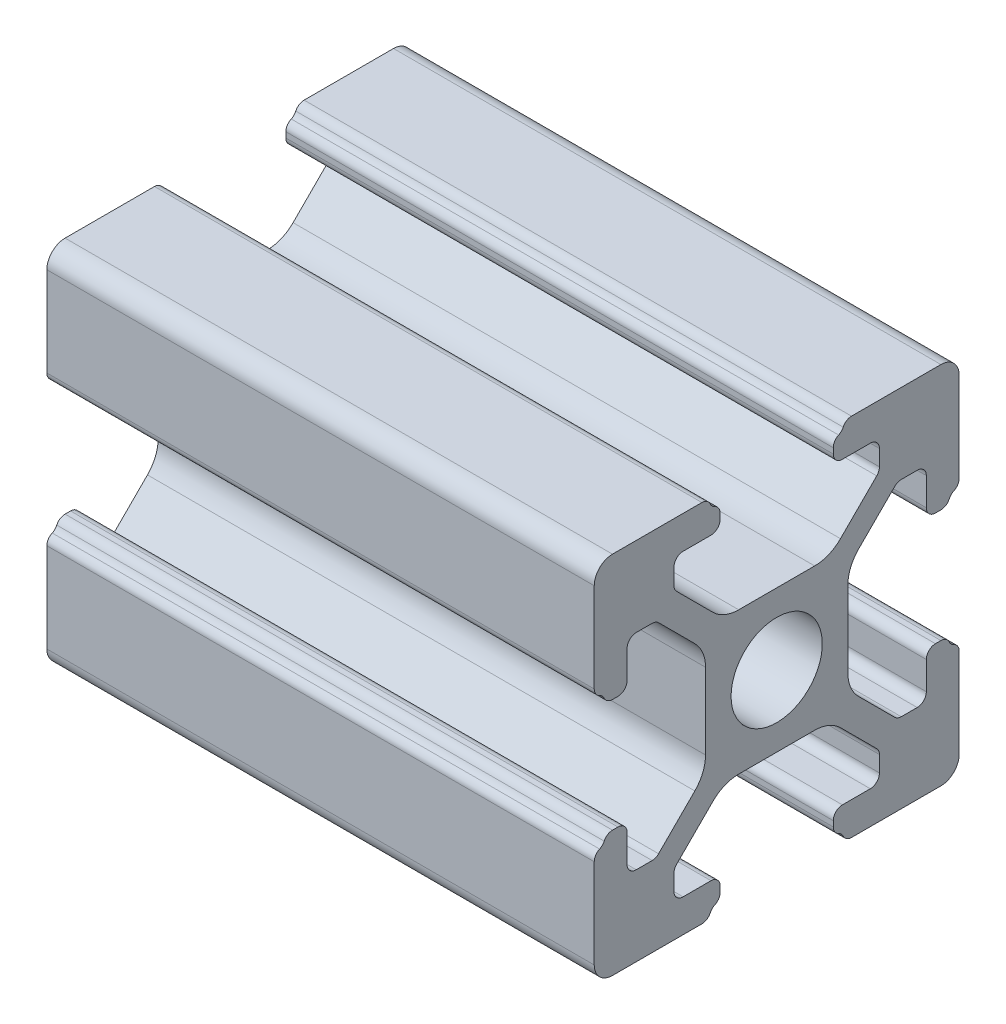
SolidWorks part; units mm, degrees
ref_plane "Front Plane" through (0, 0, 0) normal (0, 0, 1) x (1, 0, 0)
ref_plane "Top Plane" through (0, 0, 0) normal (0, 1, 0) x (1, 0, 0)
ref_plane "Right Plane" through (0, 0, 0) normal (1, 0, 0) x (0, 0, -1)
sketch "Sketch1" plane through (0, 0, 0) normal (1, 0, 0) x (0, 0, -1)
  line L0 (10, 10) -> (-10, -10) construction
  line L1 (-10, 10) -> (10, 10)
  line L2 (-10, 10) -> (-10, -10)
  line L3 (-10, -10) -> (10, -10)
  line L4 (10, 10) -> (10, -10)
  dimension "D1" = 20
extrude "Boss-Extrude1" add sketch "Sketch1" along normal blind 30
fillet "Fillet1" radius 1 4 edges at (15, -10, -10) (15, -10, 10) (15, 10, -10) (15, 10, 10)
sketch "Sketch3" plane through (0, 0, 0) normal (-1, 0, 0) x (0, 0, 1)
  line L0 (-3.6, 10) -> (3.6, 10)
  line L1 (-9, 10) -> (9, 10) construction
  line L2 (3.6, 10) -> (3.6, 9.5)
  line L3 (3.6, 9.5) -> (3.1, 9.5)
  line L4 (3.1, 9.5) -> (3.1, 8.2)
  line L5 (3.1, 8.2) -> (5.63, 8.2)
  line L6 (5.63, 8.2) -> (5.63, 6.6199)
  line L7 (5.63, 6.6199) -> (2.9101, 3.9)
  line L8 (2.9101, 3.9) -> (-2.9101, 3.9)
  line L9 (-2.9101, 3.9) -> (-5.63, 6.6199)
  line L10 (-5.63, 6.6199) -> (-5.63, 8.2)
  line L11 (-5.63, 8.2) -> (-3.1, 8.2)
  line L12 (-3.1, 8.2) -> (-3.1, 9.5)
  line L13 (-3.1, 9.5) -> (-3.6, 9.5)
  line L14 (-3.6, 9.5) -> (-3.6, 10)
  line L15 (0, 10) -> (0, 3.9) construction
  line L16 (10, 3.6) -> (10, -3.6)
  line L17 (10, -3.6) -> (9.5, -3.6)
  line L18 (9.5, -3.6) -> (9.5, -3.1)
  line L19 (9.5, -3.1) -> (8.2, -3.1)
  line L20 (8.2, -3.1) -> (8.2, -5.63)
  line L21 (8.2, -5.63) -> (6.6199, -5.63)
  line L22 (6.6199, -5.63) -> (3.9, -2.9101)
  line L23 (3.9, -2.9101) -> (3.9, 2.9101)
  line L24 (3.9, 2.9101) -> (6.6199, 5.63)
  line L25 (6.6199, 5.63) -> (8.2, 5.63)
  line L26 (8.2, 5.63) -> (8.2, 3.1)
  line L27 (8.2, 3.1) -> (9.5, 3.1)
  line L28 (9.5, 3.1) -> (9.5, 3.6)
  line L29 (9.5, 3.6) -> (10, 3.6)
  line L30 (10, 0) -> (3.9, 0) construction
  line L31 (3.6, -10) -> (-3.6, -10)
  line L32 (-3.6, -10) -> (-3.6, -9.5)
  line L33 (-3.6, -9.5) -> (-3.1, -9.5)
  line L34 (-3.1, -9.5) -> (-3.1, -8.2)
  line L35 (-3.1, -8.2) -> (-5.63, -8.2)
  line L36 (-5.63, -8.2) -> (-5.63, -6.6199)
  line L37 (-5.63, -6.6199) -> (-2.9101, -3.9)
  line L38 (-2.9101, -3.9) -> (2.9101, -3.9)
  line L39 (2.9101, -3.9) -> (5.63, -6.6199)
  line L40 (5.63, -6.6199) -> (5.63, -8.2)
  line L41 (5.63, -8.2) -> (3.1, -8.2)
  line L42 (3.1, -8.2) -> (3.1, -9.5)
  line L43 (3.1, -9.5) -> (3.6, -9.5)
  line L44 (3.6, -9.5) -> (3.6, -10)
  line L45 (0, -10) -> (0, -3.9) construction
  line L46 (-10, -3.6) -> (-10, 3.6)
  line L47 (-10, 3.6) -> (-9.5, 3.6)
  line L48 (-9.5, 3.6) -> (-9.5, 3.1)
  line L49 (-9.5, 3.1) -> (-8.2, 3.1)
  line L50 (-8.2, 3.1) -> (-8.2, 5.63)
  line L51 (-8.2, 5.63) -> (-6.6199, 5.63)
  line L52 (-6.6199, 5.63) -> (-3.9, 2.9101)
  line L53 (-3.9, 2.9101) -> (-3.9, -2.9101)
  line L54 (-3.9, -2.9101) -> (-6.6199, -5.63)
  line L55 (-6.6199, -5.63) -> (-8.2, -5.63)
  line L56 (-8.2, -5.63) -> (-8.2, -3.1)
  line L57 (-8.2, -3.1) -> (-9.5, -3.1)
  line L58 (-9.5, -3.1) -> (-9.5, -3.6)
  line L59 (-9.5, -3.6) -> (-10, -3.6)
  line L60 (-10, 0) -> (-3.9, 0) construction
  line L61 (10, 9) -> (10, -9) construction
  line L62 (-10, -9) -> (-10, 9) construction
  point P4 (0, 10)
  point P17 (0, 0)
  point P26 (10, 0)
  point P43 (0, -10)
  point P60 (-10, 0)
  point P75 (0, 0)
  dimension "D1" = 135
  dimension "D2" = 6.2
  dimension "D3" = 7.2
  dimension "D4" = 6.1
  dimension "D5" = 11.26
  dimension "D6" = 0.5
  dimension "D8" = 1.4
  dimension "D9" = 1.8
  dimension "D7" = 4
extrude "Cut-Extrude1" cut sketch "Sketch3" against normal through all
hole_wizard "Ø5.0 (5) Diameter Hole1" positions "Sketch4" profile "Sketch5" hole size "Ø5.0" standard "ANSI Metric" end condition through all
sketch "Sketch4" plane through (0, 0, 0) normal (-1, 0, 0) x (0, 0, 1)
  point P0 (0, 0)
sketch "Sketch5" plane through (0, 0, 0) normal (0, 1, 0) x (0, 0, 1)
  line L0 (0, 0) -> (0, 30)
  line L1 (0, 30) -> (2.5, 30)
  line L2 (2.5, 30) -> (2.5, 0)
  line L5 (2.5, 0) -> (0, 0)
  line L11 (0, -6.35) -> (0, 107.95) construction
  dimension "Thru Hole Dia." = 5
  dimension "Thru Hole Depth" = 30
fillet "Fillet2" radius 2 8 edges at (15, -3.9, -2.9101) (15, -3.9, 2.9101) (15, -2.9101, 3.9) (15, 2.9101, 3.9) (15, 3.9, 2.9101) (15, 3.9, -2.9101) (15, 2.9101, -3.9) (15, -2.9101, -3.9)
fillet "Fillet3" radius 0.5 20 edges at (15, 3.6, -10) (15, 3.1, -9.5) (15, 3.1, -8.2) (15, 5.63, -8.2) (15, 5.63, -6.6199) (15, 3.6, 10) (15, 3.1, 9.5) (15, 3.1, 8.2) (15, 5.63, 8.2) (15, 5.63, 6.6199) (15, 6.6199, 5.63) (15, 8.2, 5.63) (15, 8.2, 3.1) (15, 9.5, 3.1) (15, 10, 3.6) (15, 9.5, -3.1) (15, 10, -3.6) (15, 8.2, -3.1) (15, 8.2, -5.63) (15, 6.6199, -5.63)
fillet "Fillet4" radius 0.5 20 edges at (15, -3.6, 10) (15, -3.1, 9.5) (15, -3.1, 8.2) (15, -5.63, 8.2) (15, -5.63, 6.6199) (15, -6.6199, 5.63) (15, -8.2, 5.63) (15, -8.2, 3.1) (15, -10, 3.6) (15, -9.5, 3.1) (15, -10, -3.6) (15, -9.5, -3.1) (15, -8.2, -3.1) (15, -8.2, -5.63) (15, -6.6199, -5.63) (15, -5.63, -6.6199) (15, -5.63, -8.2) (15, -3.1, -8.2) (15, -3.1, -9.5) (15, -3.6, -10)
fillet "Fillet5" radius 0.5 8 edges at (15, 3.6, -9.5) (15, -3.6, -9.5) (15, -9.5, -3.6) (15, -9.5, 3.6) (15, -3.6, 9.5) (15, 3.6, 9.5) (15, 9.5, 3.6) (15, 9.5, -3.6)
